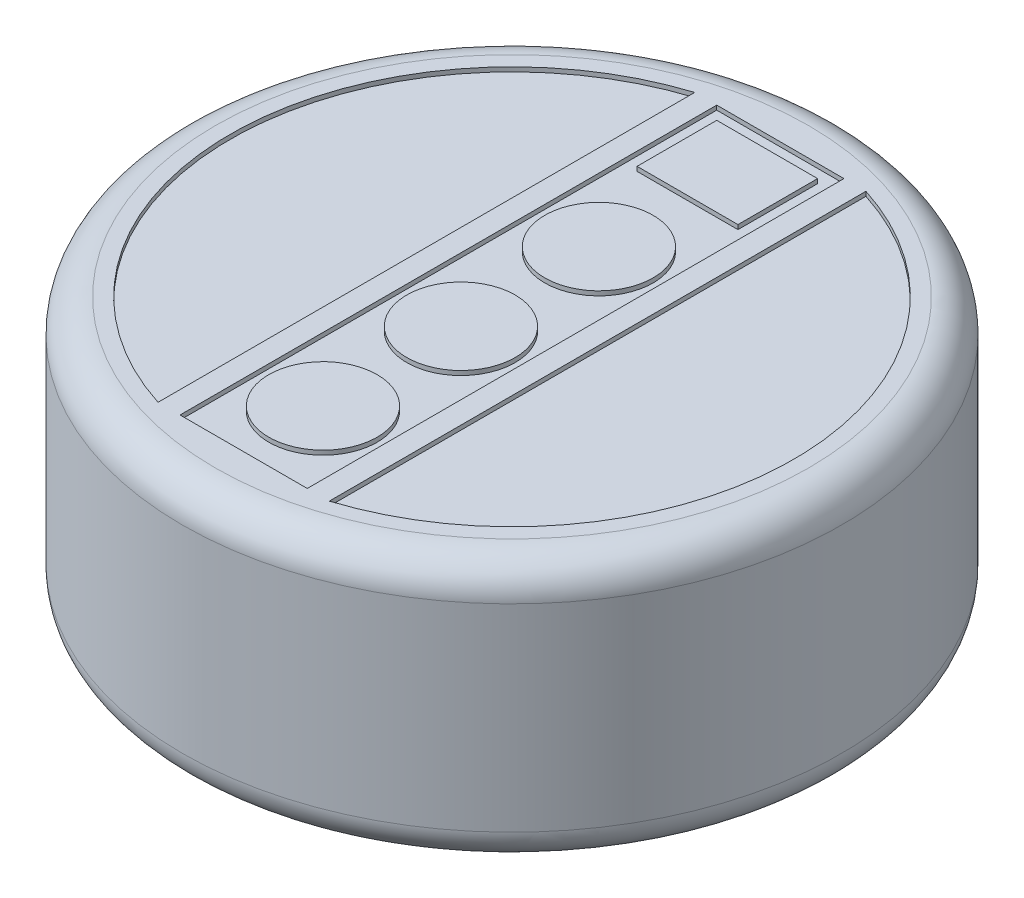
SolidWorks part; units mm, degrees
ref_plane "Front Plane" through (0, 0, 0) normal (0, 0, 1) x (1, 0, 0)
ref_plane "Top Plane" through (0, 0, 0) normal (0, 1, 0) x (1, 0, 0)
ref_plane "Right Plane" through (0, 0, 0) normal (1, 0, 0) x (0, 0, -1)
sketch "Sketch1" plane through (0, 0, 0) normal (0, 1, 0) x (1, 0, 0)
  circle A0 centre (0, 0) radius 190.5
  dimension "D1" = 381
extrude "Boss-Extrude1" add sketch "Sketch1" along normal blind 152.4 contours A0
sketch "Sketch4" plane through (0, 152.4, 0) normal (0, 1, 0) x (1, 0, 0)
  line L0 (0, 0) -> (0, 53.9768) construction
  line L1 (-49.4787, 155.1178) -> (-49.4787, -155.1178)
  line L2 (49.4787, 155.1178) -> (49.4787, -155.1178)
  line L4 (-36.7787, 155.1178) -> (36.7787, 155.1178)
  line L5 (-36.7787, 155.1178) -> (-36.7787, -155.1178)
  line L6 (-36.7787, -155.1178) -> (36.7787, -155.1178)
  line L7 (36.7787, 155.1178) -> (36.7787, -155.1178)
  arc A0 (-49.4787, 155.1178) -> (-49.4787, -155.1178) centre (0, 0) ccw
  arc A1 (49.4787, 155.1178) -> (49.4787, -155.1178) centre (0, 0) cw
  point P7 (0, 0)
  dimension "D1" = 12.7
  dimension "D2" = 12.7
extrude "Cut-Extrude2" cut sketch "Sketch4" against normal blind 2.54
sketch "Sketch5" plane through (0, 149.86, 0) normal (0, 1, 0) x (1, 0, 0)
  line L0 (0, 0) -> (50000, 0) construction
  line L1 (0, 0) -> (0, 50000) construction
  line L2 (-36.7787, 155.1178) -> (-36.7787, -155.1178) construction
  line L3 (-29.1587, 147.4978) -> (29.1587, 147.4978)
  line L4 (-29.1587, 147.4978) -> (-29.1587, 101.4563)
  line L5 (-29.1587, 101.4563) -> (29.1587, 101.4563)
  line L6 (29.1587, 147.4978) -> (29.1587, 101.4563)
  line L7 (36.7787, -155.1178) -> (36.7787, 155.1178) construction
  line L8 (36.7787, 155.1178) -> (-36.7787, 155.1178) construction
  circle A0 centre (0, 50.2503) radius 31.3345
  circle A1 centre (0, -29.5057) radius 31.3345
  circle A5 centre (0, -109.2617) radius 31.3345
  point P21 (0, 0)
  dimension "D4" = 79.756
  dimension "D1" = 7.62
  dimension "D2" = 7.62
  dimension "D3" = 7.62
  dimension "D5" = 79.756
extrude "Boss-Extrude3" add sketch "Sketch5" along normal blind 2.54
sketch "Sketch6" plane through (0, 0, 0) normal (0, -1, 0) x (1, 0, 0)
  line L1 (-166.4283, 34.4852) -> (-141.0283, 34.4852)
  line L2 (-166.4283, 34.4852) -> (-166.4283, -29.0148)
  line L3 (-166.4283, -29.0148) -> (-141.0283, -29.0148)
  line L4 (-141.0283, 34.4852) -> (-141.0283, -29.0148)
  line L5 (139.44, 34.0127) -> (164.84, 34.0127)
  line L6 (139.44, 34.0127) -> (139.44, -29.4873)
  line L7 (139.44, -29.4873) -> (164.84, -29.4873)
  line L8 (164.84, 34.0127) -> (164.84, -29.4873)
  dimension "D1" = 25.4
  dimension "D2" = 63.5
sketch "Sketch7" plane through (0, 149.86, 0) normal (0, 1, 0) x (1, 0, 0)
extrude "Cut-Extrude3" cut sketch "Sketch6" against normal blind 38.1
fillet "Fillet3" radius 19.05 2 edges at (0, 0, 190.5) (0, 152.4, 190.5)
